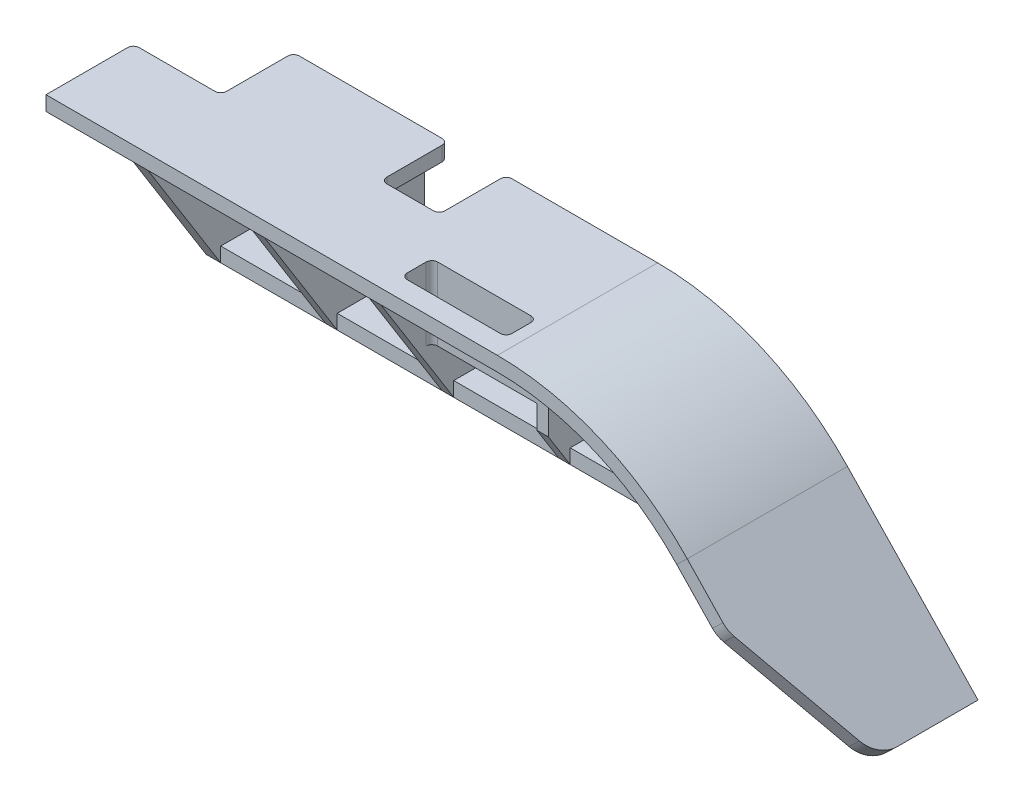
SolidWorks part; units mm, degrees
ref_plane "Front" through (0, 0, 0) normal (0, 0, 1) x (1, 0, 0)
ref_plane "Top" through (0, 0, 0) normal (0, 1, 0) x (1, 0, 0)
ref_plane "Right" through (0, 0, 0) normal (1, 0, 0) x (0, 0, -1)
sketch "Sketch1" plane through (0, 0, 0) normal (0, 1, 0) x (1, 0, 0)
  line L1 (-77.5, 27.5) -> (77.5, 27.5)
  line L2 (-77.5, 27.5) -> (-77.5, -27.5)
  line L3 (-77.5, -27.5) -> (77.5, -27.5)
  line L4 (77.5, 27.5) -> (77.5, -27.5)
  line L5 (-77.5, 27.5) -> (77.5, -27.5) construction
  line L6 (-77.5, -27.5) -> (77.5, 27.5) construction
  point P0 (0, 0)
  dimension "D1" = 155
  dimension "D2" = 55
extrude "Boss-Extrude1" add sketch "Sketch1" along normal blind 5
ref_plane "Plane1" through (0, -40, 0) normal (0, 1, 0) x (1, 0, 0)
sketch "Sketch2" plane through (0, 5, 0) normal (0, 1, 0) x (1, 0, 0)
  line L1 (-77.5, 27.5) -> (-47.5, 27.5)
  line L2 (-77.5, 27.5) -> (-77.5, 2.5)
  line L3 (-77.5, 2.5) -> (-47.5, 2.5)
  line L4 (-47.5, 27.5) -> (-47.5, 2.5)
  dimension "D1" = 25
  dimension "D2" = 30
extrude "Cut-Extrude2" cut sketch "Sketch2" against normal up to surface (5 mm away) up to face at (0, 0, 0)
sketch "Sketch3" plane through (0, 0, 0) normal (0, -1, 0) x (1, 0, 0)
  line L6 (-77.5, 27.5) -> (77.5, 27.5) construction
  line L7 (-47.5, -27.5) -> (-42.5, -27.5)
  line L8 (-47.5, -27.5) -> (-47.5, 27.5)
  line L9 (-47.5, 27.5) -> (-42.5, 27.5)
  line L10 (-42.5, -27.5) -> (-42.5, 27.5)
  dimension "D1" = 5
extrude "Boss-Extrude2" add sketch "Sketch3" along normal up to surface (40 mm away) contours L10 L9 L8 L7 up to plane "Plane1"
sketch "Sketch9" plane through (0, 0, 27.5) normal (0, 0, 1) x (1, 0, 0)
  line L0 (77.5, 5) -> (187.5, 5) construction
  line L1 (187.5, 5) -> (187.5, -70) construction
  line L2 (-77.5, 5) -> (77.5, 5) construction
  line L3 (187.5, -70) -> (142.6724, -22.931)
  line L4 (77.5, 5) -> (77.5, 0) construction
  arc A1 (142.6724, -22.931) -> (77.5, 5) centre (77.5, -85) ccw
  point P12 (141.796, 5)
  dimension "D1" = 110
  dimension "D2" = 75
sketch "Sketch10" plane through (77.5, 0, 0) normal (1, 0, 0) x (0, 0, -1)
  line L0 (-27.5, 5) -> (-27.5, -22.931) construction
  line L1 (27.5, 5) -> (-27.5, 5)
  line L2 (27.5, 5) -> (27.5, 0)
  line L3 (27.5, 0) -> (-27.5, 0)
  line L4 (-27.5, 5) -> (-27.5, 0)
sweep "Sweep1" add profiles "Sketch10" path "Sketch9"
sketch "Sketch14" plane through (0, -40, 0) normal (0, 1, 0) x (1, 0, 0)
  line L1 (-42.5, 27.5) -> (82.5, 27.5)
  line L2 (-42.5, 27.5) -> (-42.5, -2.5)
  line L3 (-42.5, -2.5) -> (82.5, -2.5)
  line L4 (82.5, 27.5) -> (82.5, -2.5)
  dimension "D1" = 125
  dimension "D2" = 30
extrude "Boss-Extrude7" add sketch "Sketch14" along normal blind 5
sketch "Sketch16" plane through (82.5, 0, 0) normal (1, 0, 0) x (0, 0, -1)
  line L1 (27.5, -35) -> (-2.5, -35)
  line L2 (27.5, -35) -> (27.5, -40)
  line L3 (27.5, -40) -> (-2.5, -40)
  line L4 (-2.5, -35) -> (-2.5, -40)
extrude "Boss-Extrude8" add sketch "Sketch16" along normal up to surface (64.7619 mm away) up to face at (161.4655, -49.9138, 0)
sketch "Sketch19" plane through (0, 0, 0) normal (0, -1, 0) x (1, 0, 0)
  line L9 (-42.5, 27.5) -> (77.5, 27.5) construction
  line L15 (77.5, -27.5) -> (73.5, -27.5)
  line L16 (77.5, -27.5) -> (77.5, 27.5)
  line L17 (77.5, 27.5) -> (73.5, 27.5)
  line L18 (73.5, -27.5) -> (73.5, 27.5)
  line L19 (37.5, -27.5) -> (37.5, 27.5)
  line L20 (37.5, -27.5) -> (33.5, -27.5)
  line L21 (33.5, -27.5) -> (33.5, 27.5)
  line L22 (37.5, 27.5) -> (33.5, 27.5)
  line L23 (-2.5, -27.5) -> (-2.5, 27.5)
  line L24 (-2.5, -27.5) -> (-6.5, -27.5)
  line L25 (-6.5, -27.5) -> (-6.5, 27.5)
  line L26 (-2.5, 27.5) -> (-6.5, 27.5)
  line L27 (77.5, -27.5) -> (37.5, -27.5) construction
  dimension "D1" = 4
  dimension "D2" = 40
extrude "Boss-Extrude9" add sketch "Sketch19" along normal up to surface (40 mm away) up to face at (20.6746, -40, 0.8333)
sketch "Sketch17" plane through (-47.5, 0, 0) normal (-1, 0, 0) x (0, 0, 1)
  line L0 (27.5, 0) -> (2.5, -40)
  line L1 (2.5, -40) -> (27.5, -40)
  line L2 (27.5, -40) -> (27.5, 0) construction
  line L3 (27.5, -40) -> (27.5, 0)
  line L5 (27.5, -40) -> (-27.5, -40) construction
  dimension "D1" = 0
extrude "Cut-Extrude4" cut sketch "Sketch17" against normal up to surface (125 mm away) up to face at (77.5, -25, 0.8333)
sketch "Sketch18" plane through (0, -35, 0) normal (0, 1, 0) x (1, 0, 0)
  line L0 (-47.5, -2.5) -> (-47.5, 27.5) construction
  line L1 (152.0238, 27.5) -> (-47.5, 27.5) construction
  circle A0 centre (-30.5, 17) radius 1.75
  circle A1 centre (69.5, 17) radius 1.75
  dimension "D1" = 3.5
  dimension "D2" = 17
  dimension "D3" = 100
  dimension "D4" = 10.5
extrude "Cut-Extrude5" cut sketch "Sketch18" against normal up to surface (5 mm away) up to face at (34.5043, -40, -2.9545)
sketch "Sketch20" plane through (0, -35, 0) normal (0, 1, 0) x (1, 0, 0)
  line L0 (77.5, 27.5) -> (77.5, -2.5) construction
  line L1 (81.5, 1.5) -> (119.5, 1.5)
  line L2 (81.5, 1.5) -> (81.5, 17.5)
  line L3 (81.5, 17.5) -> (119.5, 17.5)
  line L4 (119.5, 1.5) -> (119.5, 17.5)
  line L5 (77.5, -2.5) -> (147.2619, -2.5) construction
  dimension "D1" = 16
  dimension "D2" = 4
  dimension "D3" = 4
  dimension "D4" = 38
extrude "Cut-Extrude6" cut sketch "Sketch20" against normal up to surface (5 mm away) up to face at (-30.5, -40, -15.25)
fillet "Fillet1" radius 5 4 edges at (119.5, -37.5, -17.5) (119.5, -37.5, -1.5) (81.5, -37.5, -1.5) (81.5, -37.5, -17.5)
sketch "Sketch21" plane through (73.5, 0, 0) normal (-1, 0, 0) x (0, 0, 1)
  line L6 (27.5, 0) -> (-27.5, 0) construction
  line L11 (10, 0) -> (5, 0)
  line L12 (10, 0) -> (10, -20)
  line L13 (10, -20) -> (5, -20)
  line L14 (5, 0) -> (5, -20)
  dimension "D1" = 5
  dimension "D2" = 17.5
  dimension "D3" = 20
extrude "Boss-Extrude10" add sketch "Sketch21" along normal up to surface (36 mm away) up to face at (37.5, -22, -4.5)
sketch "Sketch22" plane through (73.5, 0, 0) normal (-1, 0, 0) x (0, 0, 1)
  line L2 (10, -28) -> (27.5, 0)
  line L3 (27.5, 0) -> (10, 0)
  line L4 (10, 0) -> (10, -28)
  line L5 (2.5, -40) -> (27.5, 0) construction
extrude "Cut-Extrude7" cut sketch "Sketch22" against normal up to surface (4 mm away) up to face at (77.5, -22, -4.5)
sketch "Sketch23" plane through (0, 0, 0) normal (0, -1, 0) x (1, 0, 0)
  line L7 (37.5, 10) -> (73.5, 10)
  line L8 (37.5, 10) -> (37.5, 20.5)
  line L9 (37.5, 20.5) -> (73.5, 20.5)
  line L10 (73.5, 10) -> (73.5, 20.5)
  line L14 (37.5, 10) -> (73.5, 10) construction
  line L15 (77.5, 27.5) -> (77.5, 10) construction
  line L16 (37.5, 10) -> (37.5, 27.5) construction
  dimension "D1" = 10.5
  dimension "D2" = 4
extrude "Cut-Extrude8" cut sketch "Sketch23" against normal up to surface (5 mm away) up to face at (-15.8333, 5, -0.8333)
fillet "Fillet2" radius 2 4 edges at (73.5, 2.5, 20.5) (73.5, 2.5, 10) (37.5, 2.5, 20.5) (37.5, -7.5, 10)
sketch "Sketch24" plane through (0, 0, 0) normal (0, -1, 0) x (1, 0, 0)
  line L0 (33.5, -27.5) -> (-2.5, -27.5) construction
  line L1 (25.5, -27.5) -> (5.5, -27.5)
  line L2 (25.5, -27.5) -> (25.5, -4.5)
  line L3 (25.5, -4.5) -> (5.5, -4.5)
  line L4 (5.5, -27.5) -> (5.5, -4.5)
  line L5 (-47.5, -2.5) -> (-47.5, -27.5) construction
  dimension "D1" = 20
  dimension "D2" = 53
  dimension "D3" = 23
extrude "Cut-Extrude9" cut sketch "Sketch24" against normal up to surface (5 mm away) up to face at (55.5, 5, 15.25)
fillet "Fillet3" radius 2 7 edges at (-47.5, 2.5, -2.5) (5.5, 2.5, -4.5) (5.5, 2.5, -27.5) (25.5, 2.5, -4.5) (25.5, 2.5, -27.5) (-47.5, -17.5, -27.5) (-77.5, 2.5, -2.5)
chamfer "Chamfer1" distance 45 angle 25 1 edges at (185.6897, -71.7241, 27.5) first distance on face at (163.2759, -48.1897, 27.5)
fillet "Fillet4" radius 10 2 edges at (154.6552, -39.1379, 27.5) (185.6897, -71.7241, 6.5162)
